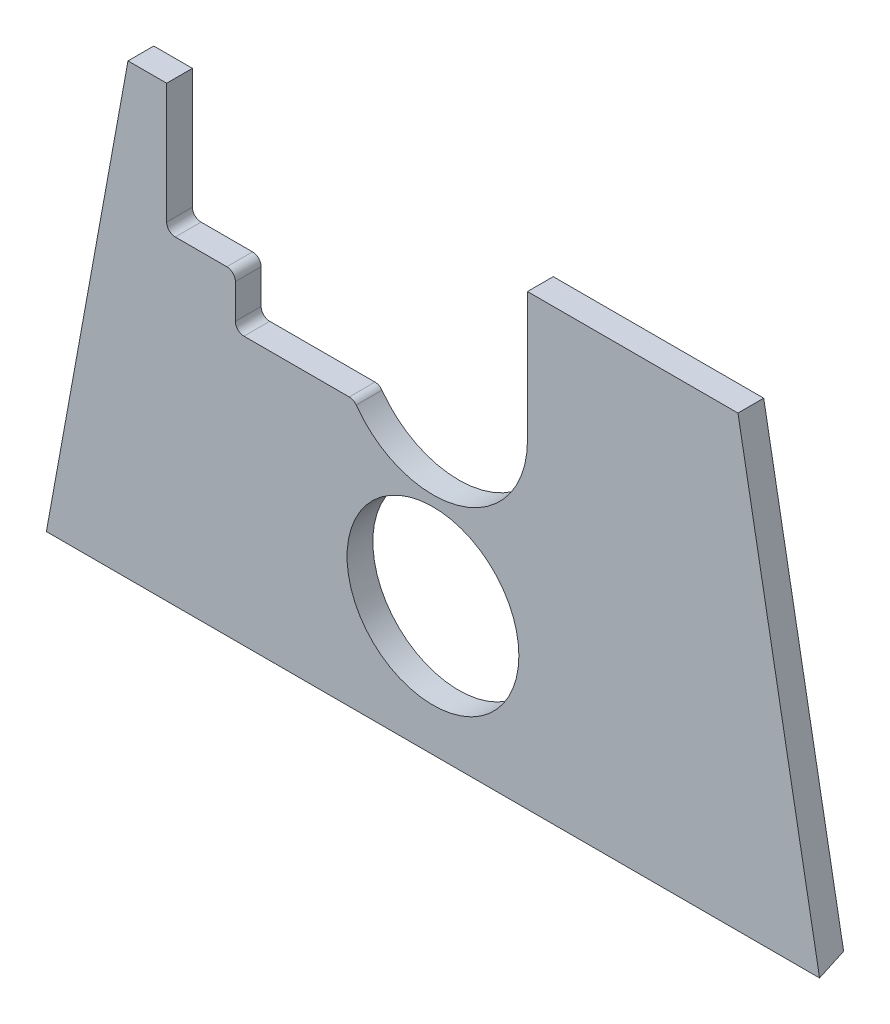
SolidWorks part; units mm, degrees
material "Acrylic (Medium-high impact)"
ref_plane "Front Plane" through (0, 0, 0) normal (0, 0, 1) x (1, 0, 0)
ref_plane "Top Plane" through (0, 0, 0) normal (0, 1, 0) x (1, 0, 0)
ref_plane "Right Plane" through (0, 0, 0) normal (1, 0, 0) x (0, 0, -1)
sketch "Sketch1" plane through (0, 0, 0) normal (0, 0, 1) x (1, 0, 0)
  line L0 (-45, 0) -> (45, 0)
  line L1 (-45, 0) -> (-35.5, 52.2)
  line L2 (-35.5, 52.2) -> (35.5, 52.2)
  line L3 (35.5, 52.2) -> (45, 0)
  point P0 (0, 52.2)
  point P4 (0, 0)
  dimension "D1" = 90
  dimension "D2" = 52.2
  dimension "D3" = 71
extrude "Boss-Extrude1" add sketch "Sketch1" along normal mid plane 3
chamfer "Chamfer1" distance 3 angle 20 1 edges at (0, 0, -1.5) first distance on face at (0, 0, 0)
sketch "Sketch2" plane through (0, 0, 1.5) normal (0, 0, 1) x (1, 0, 0)
  line L0 (0, 0) -> (0, 52.2) construction
  line L1 (-45, 0) -> (45, 0) construction
  line L2 (35.5, 52.2) -> (-35.5, 52.2) construction
  line L3 (-11, 52.2) -> (11, 52.2)
  line L4 (-11, 52.2) -> (-11, 37.2)
  line L5 (11, 37.2) -> (11, 52.2)
  line L6 (-23, 37.2) -> (-23, 31.2)
  line L7 (-11, 52.2) -> (-31, 52.2)
  line L8 (-11, 52.2) -> (-11, 37.2)
  line L9 (-11, 37.2) -> (-31, 37.2)
  line L10 (-31, 52.2) -> (-31, 37.2)
  line L11 (-23, 31.2) -> (-9.2195, 31.2)
  circle A0 centre (0, 15) radius 10
  arc A1 (-11, 37.2) -> (11, 37.2) centre (0, 37.2) ccw
  point P11 (0, 52.2)
  line M7 (35.5, 52.2) -> (-35.5, 52.2)
  dimension "D3" = 20
  dimension "D1" = 22
  dimension "D2" = 15
  dimension "D4" = 15
  dimension "D5" = 20
  dimension "D6" = 15
  dimension "D7" = 6
  dimension "D8" = 12
extrude "Cut-Extrude1" cut sketch "Sketch2" against normal through all contours L10 L9 L4 M7 | A1 L0 L3 L4 | L0 A1 L5 M7 | L0 A0 | A0 L0 | A1 L9 L6 L11 region at (-4.2441, 15, 1.5) region at (-5.1961, 40.2528, 1.5) region at (5.1961, 40.2528, 1.5) region at (4.2441, 15, 1.5) region at (-16.7027, 34.1305, 1.5) region at (-21, 44.7, 1.5)
fillet "Fillet1" radius 1 4 edges at (-31, 37.2, 0) (-9.2195, 31.2, 0) (-23, 31.2, 0) (-23, 37.2, 0)
